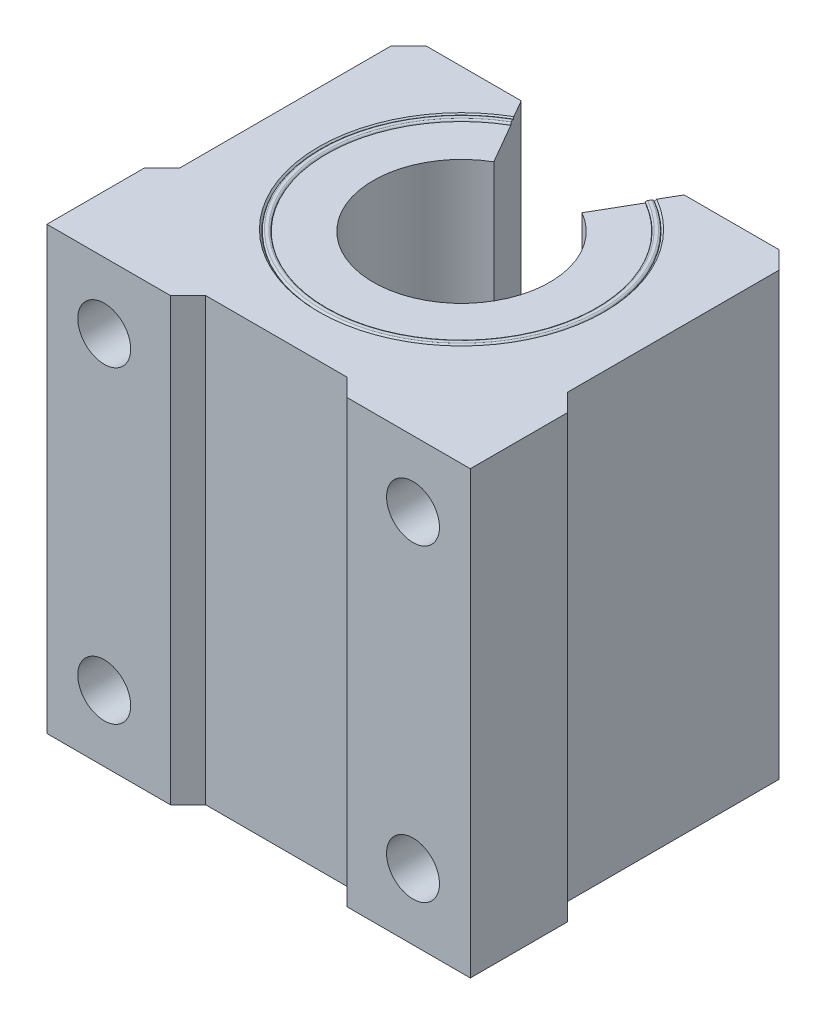
SolidWorks part; units mm, degrees
ref_plane "前视基准面" through (0, 0, 0) normal (0, 0, 1) x (1, 0, 0)
ref_plane "上视基准面" through (0, 0, 0) normal (0, 1, 0) x (1, 0, 0)
ref_plane "右视基准面" through (0, 0, 0) normal (1, 0, 0) x (0, 0, -1)
ref_plane "基准面1" through (0, -25, 0) normal (0, 1, 0) x (-1, 0, 0)
sketch "草图4" plane through (0, -25, 0) normal (0, 1, 0) x (-1, 0, 0)
  line L0 (8, 21) -> (-8, 21)
  line L1 (-8, 21) -> (-8, 23)
  line L2 (-8, 23) -> (-24, 23)
  line L3 (-24, 23) -> (-24, 12)
  line L4 (-24, 12) -> (-22, 10)
  line L5 (-22, 10) -> (-22, -16)
  line L6 (-22, -16) -> (-9.2376, -16)
  line L7 (22, -16) -> (22, 10)
  line L8 (22, 10) -> (24, 12)
  line L9 (24, 12) -> (24, 23)
  line L10 (24, 23) -> (8, 23)
  line L11 (8, 23) -> (8, 21)
  line L12 (9.2376, -16) -> (5, -8.6603)
  line L13 (-9.2376, -16) -> (-5, -8.6603)
  line L14 (49.0341, 0) -> (-54.8041, 0) construction
  line L15 (60.5, 0) -> (-60.5, 0) construction
  line L16 (0, 51.6133) -> (0, -47.1655) construction
  line L17 (0, 50.05) -> (0, -50.05) construction
  line L18 (9.2376, -16) -> (22, -16)
  arc A0 (5, -8.6603) -> (-5, -8.6603) centre (0, 0) ccw
  dimension "S" = 20
  dimension "D1" = 2
  dimension "W" = 48
  dimension "A" = 11
  dimension "G" = 39
  dimension "h2" = 23
  dimension "D6" = 135
  dimension "D7" = 135
  dimension "D" = 24
  dimension "D9" = 16
  dimension "D10" = 8
  dimension "D11" = 2
  dimension "D12" = 2
  dimension "D13" = 11
  dimension "θ" = 60
  dimension "D16" = 30
  dimension "h1" = 10
extrude "拉伸2" add sketch "草图4" along normal blind 50
chamfer "倒角1" distance 2 angle 45 2 edges at (-8, 0, 23) (8, 0, 23)
sketch "草图5" plane through (0, 0, 23) normal (0, 0, 1) x (1, 0, 0)
  line L0 (-17.5, 17.5) -> (17.5, 17.5) construction
  line L1 (17.5, 17.5) -> (17.5, -17.5) construction
  line L2 (17.5, -17.5) -> (-17.5, -17.5) construction
  line L3 (-17.5, -17.5) -> (-17.5, 17.5) construction
  line L4 (0, -50.05) -> (0, 50.05) construction
  line L5 (50.05, 0) -> (-50.05, 0) construction
  circle A0 centre (-17.5, 17.5) radius 3
  circle A1 centre (17.5, 17.5) radius 3
  circle A2 centre (17.5, -17.5) radius 3
  circle A3 centre (-17.5, -17.5) radius 3
  dimension "S1" = 6
  dimension "J" = 35
  dimension "D3" = 17.5
  dimension "K" = 35
  dimension "D4" = 17.5
extrude "切除-拉伸1" cut sketch "草图5" against normal blind 12
chamfer "倒角2" distance 2 angle 45 2 edges at (-22, 0, -16) (22, 0, -16)
sketch "草图6" plane through (0, 0, 0) normal (1, 0, 0) x (0, 0, -1)
  line L0 (-16.2, -25) -> (-16, -24.8)
  line L1 (-23, -25) -> (-12, -25) construction
  line L2 (-15.45, -25) -> (0, -25)
  line L3 (-15.25, -24.8) -> (0, -24.8)
  line L4 (0, 60.5) -> (0, -60.5) construction
  line L5 (-16.2, -25) -> (-15.7988, -25)
  line L6 (-10, -25) -> (14, -25) construction
  line L7 (0, -25) -> (0, -24.8)
  line L8 (0, -10.2649) -> (0, -26.9155) construction
  arc A0 (-16, -24.8) -> (-15.7988, -25) centre (-15.7988, -24.7988) ccw
  arc A1 (-15.25, -24.8) -> (-15.45, -25) centre (-15.45, -24.8) cw
  dimension "D6" = 0.2
  dimension "D7" = 0.2012
  dimension "D1" = 30.5
  dimension "D2" = 45
  dimension "D3" = 0.2
  dimension "dL" = 32
revolve "切除-旋转1" cut sketch "草图6" angle 360 about L8
mirror "镜向1" about plane through (0, 0, 0) normal (0, 1, 0) of "切除-旋转1"
equation "\"D11@草图4\" = \"D1@草图4\""
equation "\"D12@草图4\" = \"D1@草图4\""
equation "\"D9@草图4\" = \"W@草图4\" / 3"
equation "\"D10@草图4\" = \"W@草图4\" / 6"
equation "\"D13@草图4\" = \"A@草图4\""
equation "\"D16@草图4\" = \"θ@草图4\" / 2"
equation "\"D1@基准面1\" = \"M@拉伸2\" / 2"
equation "\"D1@倒角1\" = \"D1@草图4\""
equation "\"D3@草图5\" = \"J@草图5\" / 2"
equation "\"D4@草图5\" = \"K@草图5\" / 2"
